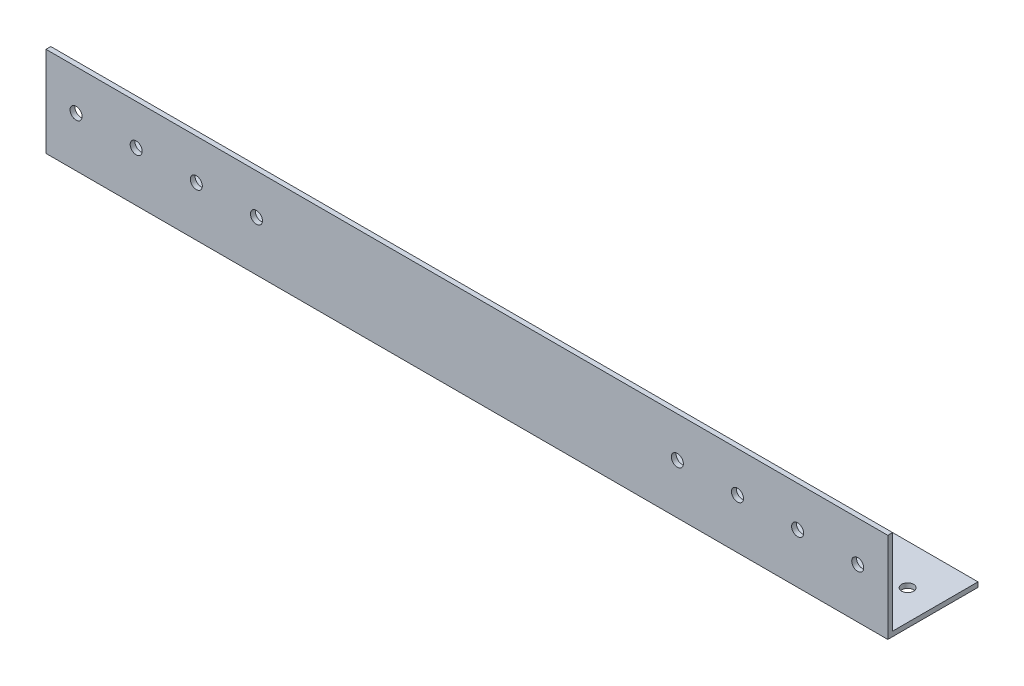
SolidWorks part; units mm, degrees
ref_plane "Спереди" through (0, 0, 0) normal (0, 0, 1) x (1, 0, 0)
ref_plane "Сверху" through (0, 0, 0) normal (0, 1, 0) x (1, 0, 0)
ref_plane "Справа" through (0, 0, 0) normal (1, 0, 0) x (0, 0, -1)
sketch "Эскиз1" plane through (0, 0, 0) normal (1, 0, 0) x (0, 0, -1)
  line L0 (0, 0) -> (0, 75)
  line L1 (0, 0) -> (75, 0)
extrude "Вытянуть-Тонкостенный1" add sketch "Эскиз1" along normal blind 700 thin thin type one direction reverse wall 4
sketch "Эскиз2" plane through (0, 0, 0) normal (0, 0, 1) x (1, 0, 0)
  line L0 (350, 0) -> (350, 127.8436) construction
  line L1 (700, 0) -> (0, 0) construction
  circle A0 centre (25, 41.5) radius 5
  circle A1 centre (75, 41.5) radius 5
  circle A2 centre (125, 41.5) radius 5
  circle A3 centre (175, 41.5) radius 5
  circle A4 centre (525, 41.5) radius 5
  circle A5 centre (575, 41.5) radius 5
  circle A6 centre (625, 41.5) radius 5
  circle A7 centre (675, 41.5) radius 5
  dimension "D1" = 4
extrude "Вырез-Вытянуть1" cut sketch "Эскиз2" against normal blind 10
sketch "Эскиз3" plane through (0, 0, 0) normal (0, -1, 0) x (1, 0, 0)
  line L0 (350, -86.8397) -> (350, 25.7387) construction
  circle A0 centre (25, -41.5) radius 5
  circle A1 centre (75, -41.5) radius 5
  circle A2 centre (125, -41.5) radius 5
  circle A3 centre (175, -41.5) radius 5
  circle A4 centre (525, -41.5) radius 5
  circle A5 centre (575, -41.5) radius 5
  circle A6 centre (625, -41.5) radius 5
  circle A7 centre (675, -41.5) radius 5
  point P18 (350, 25.7387)
  dimension "D1" = 4
extrude "Вырез-Вытянуть2" cut sketch "Эскиз3" against normal blind 10
